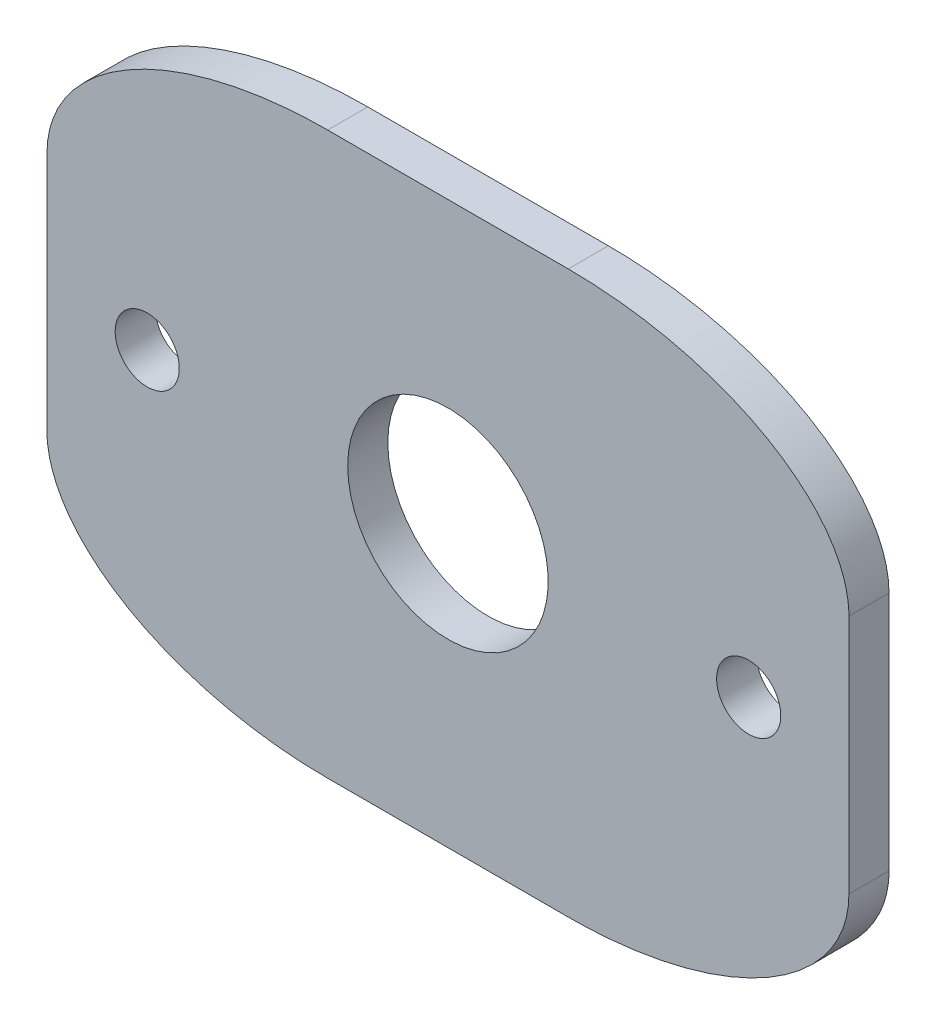
SolidWorks part; units mm, degrees
material "ABS"
ref_plane "Płaszczyzna przednia" through (0, 0, 0) normal (0, 0, 1) x (1, 0, 0)
ref_plane "Płaszczyzna górna" through (0, 0, 0) normal (0, 1, 0) x (1, 0, 0)
ref_plane "Płaszczyzna prawa" through (0, 0, 0) normal (1, 0, 0) x (0, 0, -1)
sketch "Szkic1" plane through (0, 0, 0) normal (0, 0, 1) x (1, 0, 0)
  line L1 (-20, -14) -> (20, -14)
  line L2 (-20, -14) -> (-20, 14)
  line L3 (-20, 14) -> (20, 14)
  line L4 (20, -14) -> (20, 14)
  line L5 (-20, -14) -> (20, 14) construction
  line L6 (-20, 14) -> (20, -14) construction
  point P0 (0, 0)
  dimension "D1" = 28
  dimension "D2" = 40
extrude "Dodanie-wyciągnięcie1" add sketch "Szkic1" along normal blind 2
fillet "Zaokrąglenie1" radius 14 4 edges at (-20, 14, 1) (-20, -14, 1) (20, -14, 1) (20, 14, 1) second distance 8 first distance on face at (0, 14, 1) first distance on face at (0, -14, 1)
sketch "Szkic3" plane through (0, 0, 15) normal (0, 0, 1) x (1, 0, 0)
  circle A0 centre (-15, 0) radius 1.6
  circle A1 centre (15, 0) radius 1.6
  circle A2 centre (0, 0) radius 5
  dimension "D1" = 10
  dimension "D2" = 3.2
  dimension "D3" = 3.2
extrude "Wytnij-wyciągnięcie1" cut sketch "Szkic3" against normal through all
